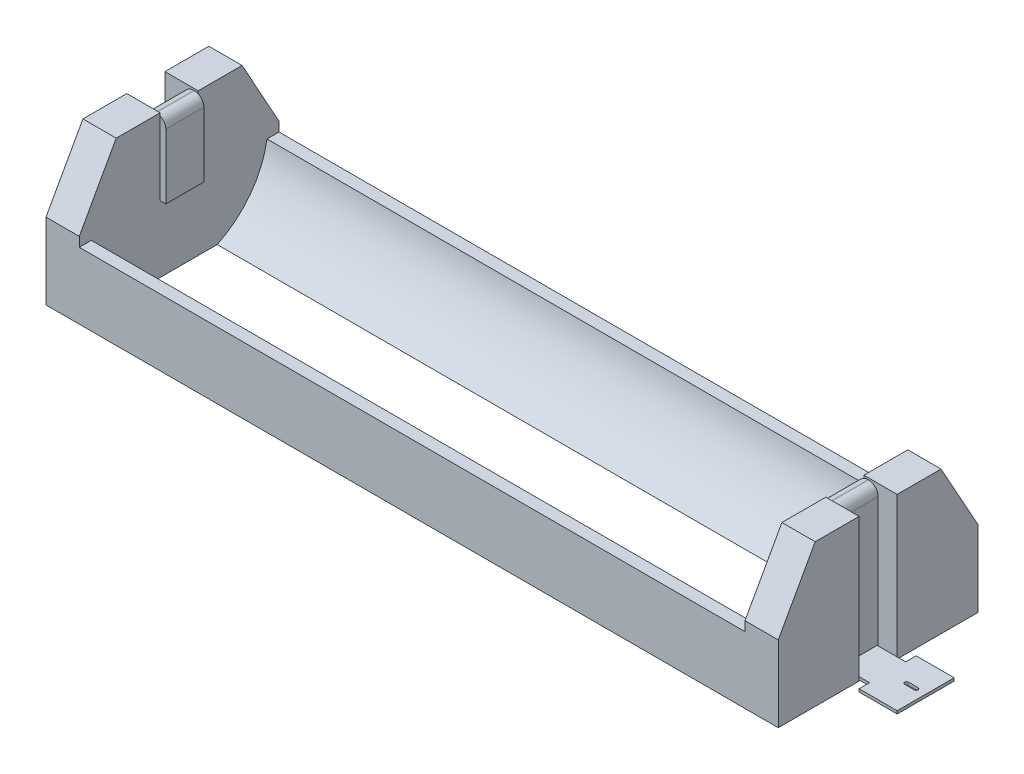
SolidWorks part; units mm, degrees
ref_plane "Płaszczyzna przednia" through (0, 0, 0) normal (0, 0, 1) x (1, 0, 0)
ref_plane "Płaszczyzna górna" through (0, 0, 0) normal (0, 1, 0) x (1, 0, 0)
ref_plane "Płaszczyzna prawa" through (0, 0, 0) normal (1, 0, 0) x (0, 0, -1)
sketch "Szkic1" plane through (0, 0, 0) normal (0, 1, 0) x (1, 0, 0)
  line L0 (0, 16.6009) -> (0, -20.6468) construction
  line L1 (-38.5, -10.5) -> (38.5, -10.5)
  line L2 (-38.5, -10.5) -> (-38.5, 10.5)
  line L3 (-38.5, 10.5) -> (38.5, 10.5)
  line L4 (38.5, -10.5) -> (38.5, 10.5)
  line L5 (-38.5, -10.5) -> (38.5, 10.5) construction
  line L6 (-38.5, 10.5) -> (38.5, -10.5) construction
  line L7 (-38.5, 10.5) -> (-35, 10.5)
  line L8 (-38.5, 10.5) -> (-38.5, -10.5)
  line L9 (-38.5, -10.5) -> (-35, -10.5)
  line L10 (-35, 10.5) -> (-35, -10.5)
  line L11 (38.5, -10.5) -> (35, -10.5)
  line L12 (35, 10.5) -> (35, -10.5)
  line L13 (38.5, 10.5) -> (35, 10.5)
  line L14 (38.5, 10.5) -> (38.5, -10.5)
  line L15 (38.5, -2) -> (38.5, 2)
  line L16 (-35, -4) -> (35, -4)
  line L17 (-35, -4) -> (-35, 4)
  line L18 (-35, 4) -> (35, 4)
  line L19 (35, -4) -> (35, 4)
  line L20 (-38.5, -2) -> (-36.5, -2)
  line L21 (-38.5, -2) -> (-38.5, 2)
  line L22 (-38.5, 2) -> (-36.5, 2)
  line L23 (-36.5, -2) -> (-36.5, 2)
  line L24 (38.5, -2) -> (36.5, -2)
  line L25 (36.5, -2) -> (36.5, 2)
  line L26 (38.5, 2) -> (36.5, 2)
  point P0 (0, 0)
  point P20 (-37.5, -2)
  dimension "D1" = 21
  dimension "D2" = 77
  dimension "D3" = 3.5
  dimension "D4" = 8
  dimension "D5" = 4
  dimension "D6" = 2
  dimension "D7" = 4
  dimension "D8" = 2
extrude "Dodanie-wyciągnięcie1" add sketch "Szkic1" along normal blind 15 contours L10 L3 L2 L1 | L3 L12 L1 L4 region at (-38.2871, 0, 6.25) region at (35.2129, 0, 7.25)
extrude "Dodanie-wyciągnięcie2" add sketch "Szkic1<3>" along normal blind 7 contours L16 L10 L1 L12 | L10 L18 L12 L3 region at (0, 0, 7.25) region at (0, 0, -7.25)
sketch "Szkic1<3>" plane through (0, 0, 0) normal (0, 1, 0) x (1, 0, 0) same geometry as "Szkic1"
sketch "Szkic2" plane through (-35, 0, 0) normal (1, 0, 0) x (0, 0, -1)
  circle A0 centre (0, 8.4512) radius 9.35
  point P3 (0, 0)
  dimension "D1" = 18.7
extrude "Wytnij-wyciągnięcie1" cut sketch "Szkic2" along normal up to surface (70 mm away) up to face at (35, 7.25, 0)
sketch "Szkic3" plane through (0, 0, 0) normal (0, 1, 0) x (1, 0, 0)
  line L0 (-36.5, 1.9) -> (-39.5, 1.9)
  line L1 (-36.5, -2) -> (-36.5, 2) construction
  line L2 (-39.5, 1.9) -> (-39.5, 3)
  line L3 (-39.5, 3) -> (-43.5, 3)
  line L4 (-43.5, 3) -> (-43.5, -3)
  line L5 (-43.5, 0) -> (-36.5, 0)
  line L6 (-36.5, -1.9) -> (-36.5, 1.9)
  line L7 (-42.5, 0) -> (-41.5, 0) construction
  line L8 (-42.5, 0.2) -> (-41.5, 0.2)
  line L9 (-42.5, -0.2) -> (-41.5, -0.2)
  line L10 (-38.5, 2) -> (-38.5, 10.5) construction
  line L11 (51.321, 0) -> (-60.425, 0) construction
  line L12 (0, -36.5173) -> (0, 27.4151) construction
  line L13 (-39.5, -3) -> (-43.5, -3)
  line L14 (-39.5, -1.9) -> (-39.5, -3)
  line L15 (-36.5, -1.9) -> (-39.5, -1.9)
  line L16 (42.5, 0) -> (41.5, 0) construction
  line L17 (42.5, 0.2) -> (41.5, 0.2)
  line L18 (42.5, -0.2) -> (41.5, -0.2)
  line L19 (36.5, -1.9) -> (39.5, -1.9)
  line L20 (39.5, -1.9) -> (39.5, -3)
  line L21 (39.5, -3) -> (43.5, -3)
  line L22 (36.5, -1.9) -> (36.5, 1.9)
  line L23 (43.5, 0) -> (36.5, 0)
  line L24 (43.5, 3) -> (43.5, -3)
  line L25 (39.5, 3) -> (43.5, 3)
  line L26 (39.5, 1.9) -> (39.5, 3)
  line L27 (36.5, 1.9) -> (39.5, 1.9)
  arc A0 (-42.5, 0.2) -> (-42.5, -0.2) centre (-42.5, 0) ccw
  arc A1 (-41.5, -0.2) -> (-41.5, 0.2) centre (-41.5, 0) ccw
  arc A2 (42.5, 0.2) -> (42.5, -0.2) centre (42.5, 0) cw
  arc A3 (41.5, -0.2) -> (41.5, 0.2) centre (41.5, 0) cw
  point P10 (-42, 0)
  point P28 (42, 0)
  dimension "D2" = 0.2
  dimension "D1" = 1
  dimension "D3" = 1
  dimension "D4" = 5
  dimension "D5" = 4
  dimension "D6" = 3
  dimension "D7" = 1.9
extrude "Dodanie-wyciągnięcie3" add sketch "Szkic3" along normal blind 0.3 contours A1 L5 L6 L0 L2 L3 L4 A0 L8 | A1 L9 A0 L5 L4 L13 L14 L15 L6 | L23 A3 L17 A2 L24 L25 L26 L27 L22 | L18 A3 L23 L22 L19 L20 L21 L24 A2 region at (-40.3484, 0, -1.3414) region at (-40.3484, 0, 1.3414) region at (40.3484, 0, -1.3414) region at (40.3484, 0, 1.3414)
chamfer "Sfazowanie1" distance 7 angle 29 4 edges at (36.75, 15, 10.5) (36.75, 15, -10.5) (-36.75, 15, -10.5) (-36.75, 15, 10.5) tangent propagation no first distance on face at (0, 9.25, 10.5) first distance on face at (0, 9.25, -10.5)
sketch "Szkic4" plane through (-35, 0, 0) normal (1, 0, 0) x (0, 0, -1)
  line L0 (2, 15) -> (2, 0) construction
  line L1 (-2, 15) -> (2, 15)
  line L2 (-2, 15) -> (-2, 7)
  line L3 (-2, 7) -> (2, 7)
  line L4 (2, 15) -> (2, 7)
  line L6 (-2, 15) -> (2, 15)
  line L7 (-2, 15) -> (-2, 14.8)
  line L8 (-2, 14.8) -> (2, 14.8)
  line L9 (2, 15) -> (2, 14.8)
  line M6 (6.6198, 15) -> (-6.6198, 15)
  dimension "D1" = 0.2
  dimension "D2" = 8
extrude "Wytnij-wyciągnięcie2" cut sketch "Szkic4" against normal up to next contours L2 L8 L4 M6 region at (-35, 14.9, 0)
extrude "Dodanie-wyciągnięcie4" add sketch "Szkic4<3>" along normal blind 0.6 contours L8 L2 L3 L4 region at (-35, 10.9, 0)
sketch "Szkic4<3>" plane through (-35, 0, 0) normal (1, 0, 0) x (0, 0, -1) same geometry as "Szkic4"
mirror "Lustro1" about plane through (0, 0, 0) normal (1, 0, 0) of "Wytnij-wyciągnięcie2", "Dodanie-wyciągnięcie4"
fillet "Zaokrąglenie1" radius 1 4 edges at (36.5, 14.8, 0) (34.4, 14.8, 0) (-34.4, 14.8, 0) (-36.5, 14.8, 0)
equation "\"D5@Szkic1\"=\"D4@Szkic1\"/2"
equation "\"D8@Szkic1\"=\"D7@Szkic1\"/2"
